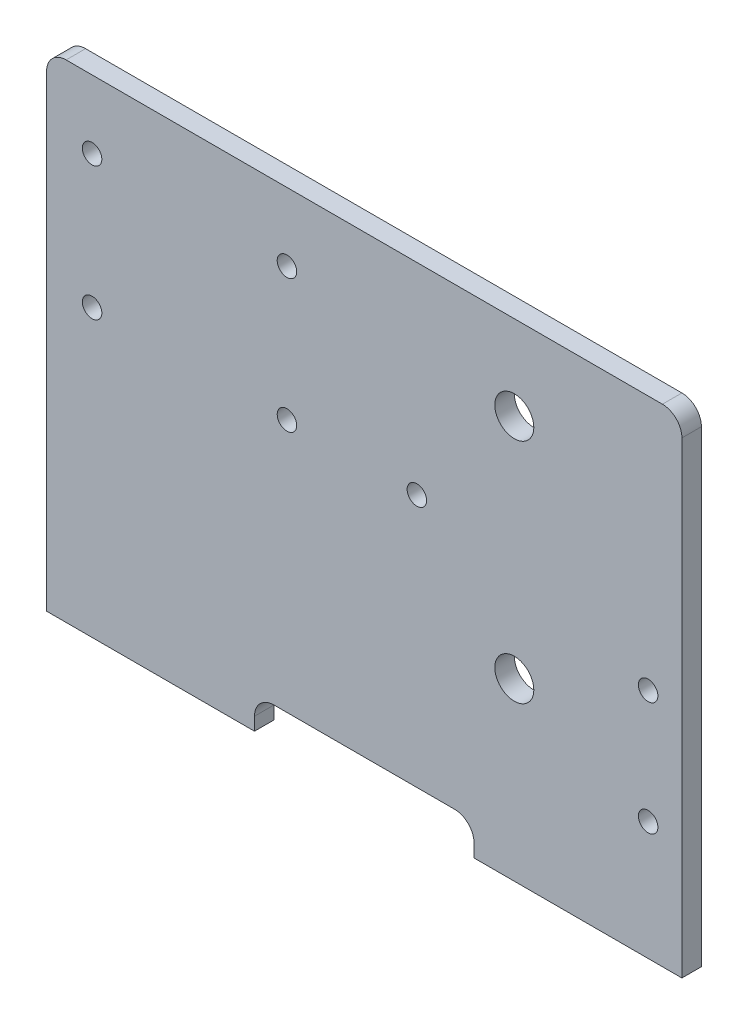
SolidWorks part; units mm, degrees
material "MDF"
ref_plane "Alzado" through (0, 0, 0) normal (0, 0, 1) x (1, 0, 0)
ref_plane "Planta" through (0, 0, 0) normal (0, 1, 0) x (1, 0, 0)
ref_plane "Vista lateral" through (0, 0, 0) normal (1, 0, 0) x (0, 0, -1)
sketch "Croquis1" plane through (0, 0, 0) normal (0, 0, 1) x (1, 0, 0)
  line L1 (-48.9, 37.5) -> (48.9, 37.5)
  line L2 (-48.9, 37.5) -> (-48.9, -37.5)
  line L3 (-48.9, -37.5) -> (48.9, -37.5)
  line L4 (48.9, 37.5) -> (48.9, -37.5)
  line L5 (-48.9, 37.5) -> (48.9, -37.5) construction
  line L6 (-48.9, -37.5) -> (48.9, 37.5) construction
  circle A0 centre (-41.9, 27) radius 1.5
  circle A3 centre (-11.9, 27) radius 1.5
  circle A4 centre (-11.9, 6.5) radius 1.5
  circle A5 centre (-41.9, 6.5) radius 1.5
  circle A6 centre (23.1, -10.5) radius 3
  circle A7 centre (23.1, 24.5) radius 3
  circle A8 centre (8.1, 6.5) radius 1.5
  circle A11 centre (43.7, -1.75) radius 1.5
  circle A12 centre (43.7, -19.25) radius 1.5
  point P0 (0, 0)
  dimension "D3" = 3
  dimension "D10" = 6
  dimension "D13" = 6
  dimension "D16" = 3
  dimension "D1" = 75
  dimension "D2" = 97.8
  dimension "D4" = 10.5
  dimension "D5" = 7
  dimension "D8" = 37
  dimension "D9" = 31
  dimension "D11" = 25.8
  dimension "D12" = 27
  dimension "D14" = 13
  dimension "D15" = 25.8
  dimension "D17" = 5.2
  dimension "D18" = 35.75
  dimension "D19" = 17.5
  dimension "D20" = 20
  dimension "D6" = 2
  dimension "D7" = 2
extrude "Saliente-Extruir1" add sketch "Croquis1" along normal mid plane 3
sketch "Croquis2" plane through (0, 0, 1.5) normal (0, 0, 1) x (1, 0, 0)
  line L0 (-48.9, 37.5) -> (-48.9, -37.5) construction
  line L1 (16.9, -37.5) -> (-16.9, -37.5)
  line L2 (16.9, -37.5) -> (16.9, -32.5)
  line L3 (16.9, -32.5) -> (-16.9, -32.5)
  line L4 (-16.9, -37.5) -> (-16.9, -32.5)
  line L5 (-48.9, -37.5) -> (48.9, -37.5) construction
  line L6 (48.9, -37.5) -> (48.9, 37.5) construction
  dimension "D1" = 5
  dimension "D2" = 32
  dimension "D3" = 32
extrude "Cortar-Extruir1" cut sketch "Croquis2" against normal through all
fillet "Redondeo1" radius 3 4 edges at (-48.9, 37.5, 0) (48.9, 37.5, 0) (16.9, -32.5, 0) (-16.9, -32.5, 0)
